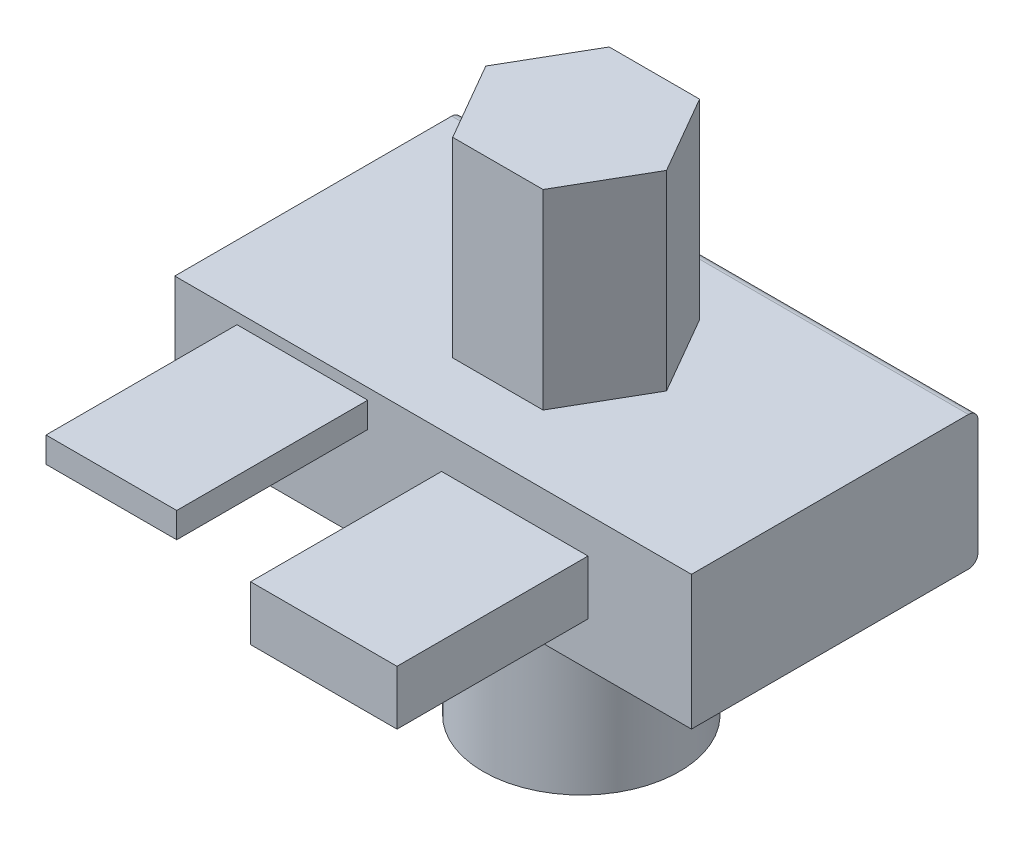
SolidWorks part; units mm, degrees
ref_plane "Front Plane" through (0, 0, 0) normal (0, 0, 1) x (1, 0, 0)
ref_plane "Top Plane" through (0, 0, 0) normal (0, 1, 0) x (1, 0, 0)
ref_plane "Right Plane" through (0, 0, 0) normal (1, 0, 0) x (0, 0, -1)
sketch "Sketch1" plane through (0, 0, 0) normal (0, 0, 1) x (1, 0, 0)
  line L1 (-68.7035, -17.821) -> (68.7035, -17.821)
  line L2 (-68.7035, -17.821) -> (-68.7035, 17.821)
  line L3 (-68.7035, 17.821) -> (68.7035, 17.821)
  line L4 (68.7035, -17.821) -> (68.7035, 17.821)
  line L5 (-68.7035, -17.821) -> (68.7035, 17.821) construction
  line L6 (-68.7035, 17.821) -> (68.7035, -17.821) construction
  point P0 (0, 0)
extrude "Boss-Extrude1" add sketch "Sketch1" along normal blind 76.2 contours L1 L4 L3 L2
sketch "Sketch2" plane through (0, 17.821, 0) normal (0, 1, 0) x (1, 0, 0)
  line L1 (23.159, -37.2907) -> (11.1437, -16.4796)
  line L2 (11.1437, -16.4796) -> (-12.8869, -16.4796)
  line L3 (-12.8869, -16.4796) -> (-24.9022, -37.2907)
  line L4 (-24.9022, -37.2907) -> (-12.8869, -58.1018)
  line L5 (-12.8869, -58.1018) -> (11.1437, -58.1018)
  line L6 (11.1437, -58.1018) -> (23.159, -37.2907)
  circle A0 centre (-0.8716, -37.2907) radius 20.8111 construction
extrude "Boss-Extrude2" add sketch "Sketch2" along normal blind 50.8
sketch "Sketch3" plane through (0, -17.821, 0) normal (0, -1, 0) x (1, 0, 0)
  circle A0 centre (0, 36.7926) radius 26.0998
extrude "Boss-Extrude3" add sketch "Sketch3" along normal blind 50.8
sketch "Sketch4" plane through (0, 0, 76.2) normal (0, 0, 1) x (1, 0, 0)
  line L1 (-52.1439, 14.8868) -> (-17.3813, 14.8868)
  line L2 (-52.1439, 14.8868) -> (-52.1439, 8.1274)
  line L3 (-52.1439, 8.1274) -> (-17.3813, 8.1274)
  line L4 (-17.3813, 14.8868) -> (-17.3813, 8.1274)
  line L5 (-52.1439, 14.8868) -> (-17.3813, 8.1274) construction
  line L6 (-52.1439, 8.1274) -> (-17.3813, 14.8868) construction
  line L7 (2.2531, 8.2883) -> (41.2001, 8.2883)
  line L8 (2.2531, 8.2883) -> (2.2531, -6.1961)
  line L9 (2.2531, -6.1961) -> (41.2001, -6.1961)
  line L10 (41.2001, 8.2883) -> (41.2001, -6.1961)
  line L11 (2.2531, 8.2883) -> (41.2001, -6.1961) construction
  line L12 (2.2531, -6.1961) -> (41.2001, 8.2883) construction
  point P0 (-34.7626, 11.5071)
  point P5 (21.7266, 1.0461)
extrude "Boss-Extrude4" add sketch "Sketch4" along normal blind 50.8
fillet "Fillet1" radius 2.54 1 edges at (0, -17.821, 10.6929)
fillet "Fillet2" radius 2.54 2 edges at (0, -17.821, 0) (0, 17.821, 0)
